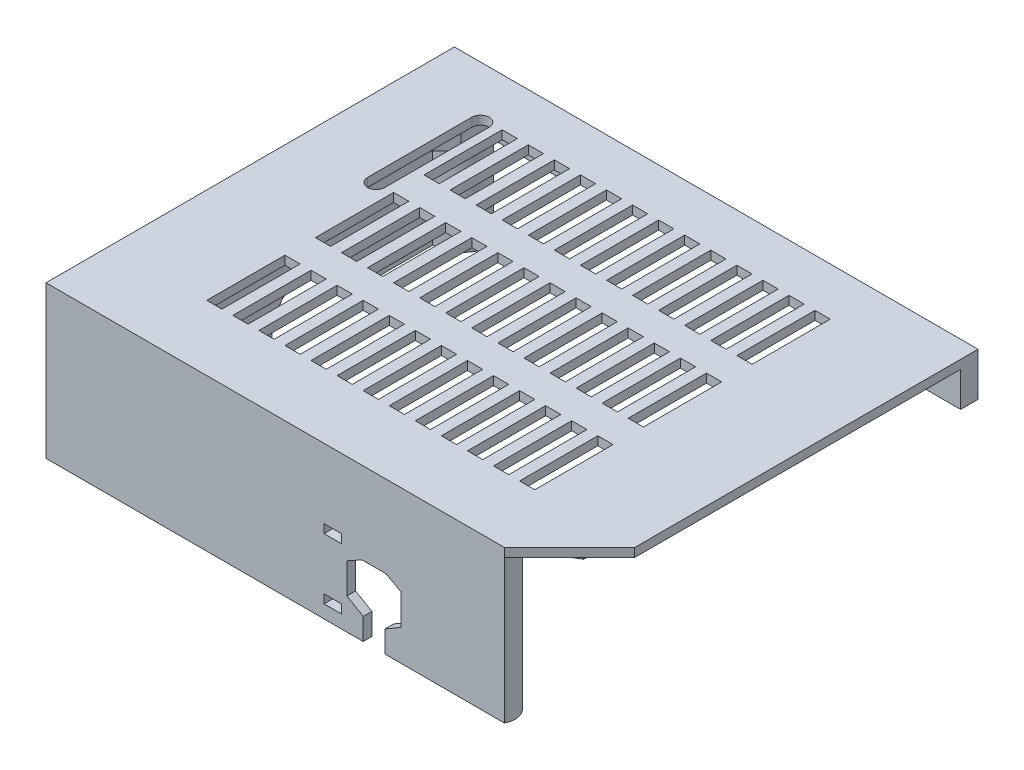
SolidWorks part; units mm, degrees
material "ABS"
ref_plane "Front" through (0, 0, 0) normal (0, 0, 1) x (1, 0, 0)
ref_plane "Top" through (0, 0, 0) normal (0, 1, 0) x (1, 0, 0)
ref_plane "Right" through (0, 0, 0) normal (1, 0, 0) x (0, 0, -1)
sketch "Esquisse1" plane through (0, 0, 0) normal (0, 0, 1) x (1, 0, 0)
  line L0 (0, 0) -> (105.5, 0)
  line L1 (105.5, 0) -> (105.5, -35)
  line L2 (105.5, -35) -> (78, -35)
  line L3 (78, -35) -> (78, -30)
  line L4 (78, -30) -> (81.75, -27.7955)
  line L5 (81.75, -27.7955) -> (81.75, -20.7955)
  line L6 (81.75, -20.7955) -> (78.25, -18.859)
  line L7 (78.25, -18.859) -> (72.75, -18.859)
  line L8 (72.75, -18.859) -> (69.25, -20.7955)
  line L9 (69.25, -20.7955) -> (69.25, -27.7955)
  line L10 (69.25, -27.7955) -> (73, -30)
  line L11 (73, -30) -> (73, -35)
  line L12 (73, -35) -> (0, -35)
  line L13 (0, -35) -> (0, 0)
  line L15 (64, -16) -> (68, -16)
  line L16 (64, -16) -> (64, -18)
  line L17 (64, -18) -> (68, -18)
  line L18 (68, -16) -> (68, -18)
  line L19 (64, -30) -> (68, -30)
  line L20 (64, -30) -> (64, -32)
  line L21 (64, -32) -> (68, -32)
  line L22 (68, -30) -> (68, -32)
  dimension "D1" = 35
  dimension "D2" = 105.5
  dimension "D3" = 5
  dimension "D4" = 4.35
  dimension "D5" = 7
  dimension "D6" = 4
  dimension "D7" = 27.5
  dimension "D8" = 5
  dimension "D9" = 12.5
  dimension "D10" = 5.5
  dimension "D11" = 12
  dimension "D12" = 2
  dimension "D13" = 4
  dimension "D14" = 37.5
  dimension "D15" = 3
extrude "Boss.-Extru.1" add sketch "Esquisse1" along normal blind 2
sketch "Esquisse3" plane through (0, 0, 0) normal (0, 0, -1) x (-1, 0, 0)
  line L0 (-105.5, 0) -> (0, 0) construction
  line L1 (-2, 0) -> (0, 0)
  line L2 (-2, 0) -> (-2, -35)
  line L3 (-2, -35) -> (0, -35)
  line L4 (0, 0) -> (0, -35)
  line L5 (0, -35) -> (-73, -35) construction
  line L6 (0, 0) -> (0, -35) construction
  dimension "D1" = 35
  dimension "D2" = 2
extrude "Boss.-Extru.2" add sketch "Esquisse3" along normal blind 92
sketch "Esquisse4" plane through (0, 0, 0) normal (0, 0, -1) x (-1, 0, 0)
  line L0 (-2, 0) -> (-2, -35) construction
  line L1 (-120.5, 0) -> (-2, 0)
  line L2 (-120.5, 0) -> (-120.5, -2)
  line L3 (-120.5, -2) -> (-2, -2)
  line L4 (-2, 0) -> (-2, -2)
  line L5 (-105.5, 0) -> (-2, 0) construction
  dimension "D1" = 2
  dimension "D2" = 118.5
extrude "Boss.-Extru.3" add sketch "Esquisse4" along normal blind 92 and the other way blind 2
chamfer "Chanfrein3" distance 15 angle 45 1 edges at (120.5, -1, 2)
sketch "Esquisse5" plane through (0, -2, 0) normal (0, -1, 0) x (1, 0, 0)
  line L0 (18, -80) -> (18, -56) construction
  line L1 (16, -80) -> (16, -56)
  line L2 (20, -80) -> (20, -56)
  line L3 (2, 0) -> (2, -92) construction
  line L4 (2, 0) -> (73, 0) construction
  line L5 (120.5, -92) -> (2, -92) construction
  line L6 (22, -81) -> (25.5, -81)
  line L7 (22, -81) -> (22, -63)
  line L8 (22, -63) -> (25.5, -63)
  line L9 (25.5, -81) -> (25.5, -63)
  line L10 (22, -56) -> (25.5, -56)
  line L11 (22, -56) -> (22, -38)
  line L12 (22, -38) -> (25.5, -38)
  line L13 (25.5, -56) -> (25.5, -38)
  line L14 (22, -31) -> (25.5, -31)
  line L15 (22, -31) -> (22, -13)
  line L16 (22, -13) -> (25.5, -13)
  line L17 (25.5, -31) -> (25.5, -13)
  line L18 (28, -31) -> (28, -13)
  line L19 (28, -31) -> (31.5, -31)
  line L20 (31.5, -31) -> (31.5, -13)
  line L21 (28, -13) -> (31.5, -13)
  line L22 (28, -56) -> (28, -38)
  line L23 (28, -56) -> (31.5, -56)
  line L24 (31.5, -56) -> (31.5, -38)
  line L25 (28, -38) -> (31.5, -38)
  line L26 (28, -81) -> (28, -63)
  line L27 (28, -81) -> (31.5, -81)
  line L28 (31.5, -81) -> (31.5, -63)
  line L29 (28, -63) -> (31.5, -63)
  line L30 (34, -31) -> (34, -13)
  line L31 (34, -31) -> (37.5, -31)
  line L32 (37.5, -31) -> (37.5, -13)
  line L33 (34, -13) -> (37.5, -13)
  line L34 (34, -56) -> (34, -38)
  line L35 (34, -56) -> (37.5, -56)
  line L36 (37.5, -56) -> (37.5, -38)
  line L37 (34, -38) -> (37.5, -38)
  line L38 (34, -81) -> (34, -63)
  line L39 (34, -81) -> (37.5, -81)
  line L40 (37.5, -81) -> (37.5, -63)
  line L41 (34, -63) -> (37.5, -63)
  line L42 (40, -31) -> (40, -13)
  line L43 (40, -31) -> (43.5, -31)
  line L44 (43.5, -31) -> (43.5, -13)
  line L45 (40, -13) -> (43.5, -13)
  line L46 (40, -56) -> (40, -38)
  line L47 (40, -56) -> (43.5, -56)
  line L48 (43.5, -56) -> (43.5, -38)
  line L49 (40, -38) -> (43.5, -38)
  line L50 (40, -81) -> (40, -63)
  line L51 (40, -81) -> (43.5, -81)
  line L52 (43.5, -81) -> (43.5, -63)
  line L53 (40, -63) -> (43.5, -63)
  line L54 (46, -31) -> (46, -13)
  line L55 (46, -31) -> (49.5, -31)
  line L56 (49.5, -31) -> (49.5, -13)
  line L57 (46, -13) -> (49.5, -13)
  line L58 (46, -56) -> (46, -38)
  line L59 (46, -56) -> (49.5, -56)
  line L60 (49.5, -56) -> (49.5, -38)
  line L61 (46, -38) -> (49.5, -38)
  line L62 (46, -81) -> (46, -63)
  line L63 (46, -81) -> (49.5, -81)
  line L64 (49.5, -81) -> (49.5, -63)
  line L65 (46, -63) -> (49.5, -63)
  line L66 (52, -31) -> (52, -13)
  line L67 (52, -31) -> (55.5, -31)
  line L68 (55.5, -31) -> (55.5, -13)
  line L69 (52, -13) -> (55.5, -13)
  line L70 (52, -56) -> (52, -38)
  line L71 (52, -56) -> (55.5, -56)
  line L72 (55.5, -56) -> (55.5, -38)
  line L73 (52, -38) -> (55.5, -38)
  line L74 (52, -81) -> (52, -63)
  line L75 (52, -81) -> (55.5, -81)
  line L76 (55.5, -81) -> (55.5, -63)
  line L77 (52, -63) -> (55.5, -63)
  line L78 (58, -31) -> (58, -13)
  line L79 (58, -31) -> (61.5, -31)
  line L80 (61.5, -31) -> (61.5, -13)
  line L81 (58, -13) -> (61.5, -13)
  line L82 (58, -56) -> (58, -38)
  line L83 (58, -56) -> (61.5, -56)
  line L84 (61.5, -56) -> (61.5, -38)
  line L85 (58, -38) -> (61.5, -38)
  line L86 (58, -81) -> (58, -63)
  line L87 (58, -81) -> (61.5, -81)
  line L88 (61.5, -81) -> (61.5, -63)
  line L89 (58, -63) -> (61.5, -63)
  line L90 (64, -31) -> (64, -13)
  line L91 (64, -31) -> (67.5, -31)
  line L92 (67.5, -31) -> (67.5, -13)
  line L93 (64, -13) -> (67.5, -13)
  line L94 (64, -56) -> (64, -38)
  line L95 (64, -56) -> (67.5, -56)
  line L96 (67.5, -56) -> (67.5, -38)
  line L97 (64, -38) -> (67.5, -38)
  line L98 (64, -81) -> (64, -63)
  line L99 (64, -81) -> (67.5, -81)
  line L100 (67.5, -81) -> (67.5, -63)
  line L101 (64, -63) -> (67.5, -63)
  line L102 (70, -31) -> (70, -13)
  line L103 (70, -31) -> (73.5, -31)
  line L104 (73.5, -31) -> (73.5, -13)
  line L105 (70, -13) -> (73.5, -13)
  line L106 (70, -56) -> (70, -38)
  line L107 (70, -56) -> (73.5, -56)
  line L108 (73.5, -56) -> (73.5, -38)
  line L109 (70, -38) -> (73.5, -38)
  line L110 (70, -81) -> (70, -63)
  line L111 (70, -81) -> (73.5, -81)
  line L112 (73.5, -81) -> (73.5, -63)
  line L113 (70, -63) -> (73.5, -63)
  line L114 (76, -31) -> (76, -13)
  line L115 (76, -31) -> (79.5, -31)
  line L116 (79.5, -31) -> (79.5, -13)
  line L117 (76, -13) -> (79.5, -13)
  line L118 (76, -56) -> (76, -38)
  line L119 (76, -56) -> (79.5, -56)
  line L120 (79.5, -56) -> (79.5, -38)
  line L121 (76, -38) -> (79.5, -38)
  line L122 (76, -81) -> (76, -63)
  line L123 (76, -81) -> (79.5, -81)
  line L124 (79.5, -81) -> (79.5, -63)
  line L125 (76, -63) -> (79.5, -63)
  line L126 (82, -31) -> (82, -13)
  line L127 (82, -31) -> (85.5, -31)
  line L128 (85.5, -31) -> (85.5, -13)
  line L129 (82, -13) -> (85.5, -13)
  line L130 (82, -56) -> (82, -38)
  line L131 (82, -56) -> (85.5, -56)
  line L132 (85.5, -56) -> (85.5, -38)
  line L133 (82, -38) -> (85.5, -38)
  line L134 (82, -81) -> (82, -63)
  line L135 (82, -81) -> (85.5, -81)
  line L136 (85.5, -81) -> (85.5, -63)
  line L137 (82, -63) -> (85.5, -63)
  line L138 (88, -31) -> (88, -13)
  line L139 (88, -31) -> (91.5, -31)
  line L140 (91.5, -31) -> (91.5, -13)
  line L141 (88, -13) -> (91.5, -13)
  line L142 (88, -56) -> (88, -38)
  line L143 (88, -56) -> (91.5, -56)
  line L144 (91.5, -56) -> (91.5, -38)
  line L145 (88, -38) -> (91.5, -38)
  line L146 (88, -81) -> (88, -63)
  line L147 (88, -81) -> (91.5, -81)
  line L148 (91.5, -81) -> (91.5, -63)
  line L149 (88, -63) -> (91.5, -63)
  line L150 (94, -31) -> (94, -13)
  line L151 (94, -31) -> (97.5, -31)
  line L152 (97.5, -31) -> (97.5, -13)
  line L153 (94, -13) -> (97.5, -13)
  line L154 (94, -56) -> (94, -38)
  line L155 (94, -56) -> (97.5, -56)
  line L156 (97.5, -56) -> (97.5, -38)
  line L157 (94, -38) -> (97.5, -38)
  line L158 (94, -81) -> (94, -63)
  line L159 (94, -81) -> (97.5, -81)
  line L160 (97.5, -81) -> (97.5, -63)
  line L161 (94, -63) -> (97.5, -63)
  arc A0 (16, -80) -> (20, -80) centre (18, -80) ccw
  arc A1 (20, -56) -> (16, -56) centre (18, -56) ccw
  point P2 (18, -68)
  dimension "D1" = 14
  dimension "D2" = 24
  dimension "D3" = 4
  dimension "D4" = 56
  dimension "D5" = 11
  dimension "D6" = 18
  dimension "D7" = 3.5
  dimension "D8" = 7
  dimension "D9" = 7
  dimension "D10" = 2
  dimension "D11" = 13
extrude "Enlèv. mat.-Extru.1" cut sketch "Esquisse5" against normal blind 92
sketch "Esquisse6" plane through (0, -2, 0) normal (0, -1, 0) x (1, 0, 0)
  line L0 (13.5, 0) -> (13.5, -12)
  line L1 (105.5, 0) -> (2, 0) construction
  line L2 (13.5, -12) -> (5.5, -20)
  line L3 (5.5, -20) -> (2, -20)
  line L4 (2, 0) -> (2, -92) construction
  line L5 (13.5, -92) -> (13.5, -80)
  line L6 (120.5, -92) -> (2, -92) construction
  line L7 (13.5, -80) -> (5.5, -72)
  line L8 (5.5, -72) -> (2, -72)
  line L9 (104.2369, -82) -> (99.4737, -79.25)
  line L10 (99.4737, -79.25) -> (99.4737, -73.75)
  line L11 (99.4737, -73.75) -> (104.2369, -71)
  line L12 (104.2369, -71) -> (109, -73.75)
  line L13 (109, -73.75) -> (109, -79.25)
  line L14 (109, -79.25) -> (104.2369, -82)
  line L15 (104.2369, -21) -> (99.4737, -18.25)
  line L16 (99.4737, -18.25) -> (99.4737, -12.75)
  line L17 (99.4737, -12.75) -> (104.2369, -10)
  line L18 (104.2369, -10) -> (109, -12.75)
  line L19 (109, -12.75) -> (109, -18.25)
  line L20 (109, -18.25) -> (104.2369, -21)
  line L21 (78, 2) -> (105.5, 2) construction
  line L22 (120.5, -13) -> (120.5, -92) construction
  line L23 (2, -20) -> (2, 0)
  line L24 (2, 0) -> (13.5, 0)
  line L25 (2, -72) -> (2, -92)
  line L26 (2, -92) -> (13.5, -92)
  dimension "D1" = 20
  dimension "D2" = 20
  dimension "D3" = 11.5
  dimension "D4" = 135
  dimension "D5" = 3.5
  dimension "D6" = 135
  dimension "D7" = 3.5
  dimension "D8" = 5.5
  dimension "D9" = 5.5
  dimension "D10" = 50
  dimension "D11" = 12
  dimension "D12" = 11.5
  dimension "D13" = 11
  dimension "D14" = 120
  dimension "D15" = 120
  dimension "D16" = 120
  dimension "D17" = 120
extrude "Boss.-Extru.4" add sketch "Esquisse6" along normal blind 6
sketch "Esquisse7" plane through (0, -8, 0) normal (0, -1, 0) x (-1, 0, 0)
  line L0 (-109, 15.5) -> (-99.4737, 15.5) construction
  line L1 (-109, 18.25) -> (-109, 12.75) construction
  line L2 (-99.4737, 12.75) -> (-99.4737, 18.25) construction
  line L3 (-109, 76.5) -> (-99.4737, 76.5) construction
  line L4 (-109, 79.25) -> (-109, 73.75) construction
  line L5 (-99.4737, 73.75) -> (-99.4737, 79.25) construction
  line L6 (-104.2369, 10) -> (-104.2369, 21) construction
  line L7 (-104.2369, 21) -> (-104.2369, 82) construction
  circle A0 centre (-104.2369, 15.5) radius 2.5
  circle A1 centre (-104.2369, 76.5) radius 2.5
  circle A2 centre (-5.4987, 76.5) radius 2.5
  circle A3 centre (-5.4987, 15.5) radius 2.5
  dimension "D1" = 5
extrude "Enlèv. mat.-Extru.2" cut sketch "Esquisse7" against normal blind 4
sketch "Esquisse8" plane through (0, -2, 0) normal (0, -1, 0) x (1, 0, 0)
  line L0 (2, -92) -> (2, 0) construction
  line L1 (13.5, 0) -> (2, 0) construction
  line L2 (2, -92) -> (13.5, -92) construction
  line L3 (56, 0) -> (56, -3.5)
  line L4 (105.5, 0) -> (13.5, 0) construction
  line L5 (56, -3.5) -> (58.8028, -6.3028)
  line L6 (58.8028, -6.3028) -> (62.6972, -6.3028)
  line L7 (62.6972, -6.3028) -> (65.5, -3.5)
  line L8 (65.5, -3.5) -> (65.5, 0)
  line L9 (65.5, 0) -> (56, 0)
  line L10 (2, 0) -> (9, 0)
  line L11 (2, -7) -> (2, 0)
  line L12 (2, -85) -> (2, -92)
  line L13 (2, -92) -> (9, -92)
  line L14 (120.5, -92) -> (13.5, -92) construction
  line L15 (65.5, 0) -> (71, 0)
  line L16 (65.5, 0) -> (65.5, -1.5)
  line L17 (65.5, -1.5) -> (71, -1.5)
  line L18 (71, 0) -> (71, -1.5)
  line L19 (7.7446, -88) -> (31.7446, -88)
  line L22 (31.7446, -88) -> (31.7446, -92)
  line L23 (120.5, -13) -> (120.5, -92) construction
  line L25 (31.7446, -88) -> (31.7446, -92)
  line L27 (96.5, -88) -> (96.5, -92)
  line L32 (96.5, -92) -> (120.5, -92)
  line L34 (96.5, -88) -> (120.5, -88)
  line L35 (120.5, -92) -> (120.5, -88)
  line L36 (96.5, -88) -> (96.5, -92)
  line L37 (31.7446, -92) -> (9, -92)
  line L38 (0, 2) -> (0, -92) construction
  line L39 (105.5, 2) -> (98.5359, 2)
  line L41 (31.7446, -89) -> (96.5, -89)
  line L42 (31.7446, -89) -> (31.7446, -92)
  line L43 (31.7446, -92) -> (96.5, -92)
  line L44 (96.5, -89) -> (96.5, -92)
  arc A0 (2, -7) -> (9, 0) centre (2, 0) ccw
  arc A1 (2, -85) -> (9, -92) centre (2, -92) cw
  circle A2 centre (102, 0) radius 4
  dimension "D9" = 102
  dimension "D10" = 8
  dimension "D1" = 9.5
  dimension "D2" = 3.5
  dimension "D3" = 54
  dimension "D4" = 6.3028
  dimension "D5" = 5.5
  dimension "D6" = 1.5
  dimension "D7" = 7
  dimension "D8" = 7
  dimension "D11" = 4
  dimension "D12" = 22.7446
  dimension "D13" = 24
  dimension "D14" = 3
extrude "Boss.-Extru.5" add sketch "Esquisse8" along normal up to surface (33 mm away) contours L39 A2 | L8 L9 L3 L5 L6 L7 | A1 L12 L13 | L10 A0 L11 region at (60.75, -2, -2.8166) region at (4.9709, -2, -89.0291) region at (102, -2, -0.6853) up to face at (25, -35, -30)
extrude "Boss.-Extru.9" add sketch "Esquisse8<5>" along normal blind 3 contours L25 L43 L36 L41 | L15 L18 L17 L16 region at (64.1223, -2, -90.5)
sketch "Esquisse8<5>" plane through (0, -2, 0) normal (0, -1, 0) x (1, 0, 0) same geometry as "Esquisse8"
extrude "Boss.-Extru.12" add sketch "Esquisse8<6>" along normal blind 8 contours L19 A1 L37 L25 L22 | L32 L35 L34 L27 L36 region at (20.1682, -2, -89.9823) region at (108.5, -2, -90)
sketch "Esquisse8<6>" plane through (0, -2, 0) normal (0, -1, 0) x (1, 0, 0) same geometry as "Esquisse8"
sketch "Esquisse9" plane through (0, -35, 0) normal (0, -1, 0) x (1, 0, 0)
  line L0 (0, 2) -> (73, 2) construction
  line L1 (0, 2) -> (0, -92) construction
  line L2 (9, -92) -> (0, -92) construction
  line L4 (56, -3.5) -> (56, 0) construction
  circle A0 centre (3.5, -1.5) radius 2
  circle A1 centre (60.75, -1.5) radius 2
  circle A2 centre (3.5, -88.5) radius 2
  dimension "D1" = 4
  dimension "D2" = 3.5
  dimension "D3" = 3.5
  dimension "D4" = 3.5
  dimension "D5" = 4.75
extrude "Enlèv. mat.-Extru.3" cut sketch "Esquisse9" against normal blind 5
sketch "Esquisse10" plane through (0, 0, -92) normal (0, 0, -1) x (-1, 0, 0)
  line L0 (0, 0) -> (-120.5, 0) construction
  line L1 (0, -35) -> (0, 0) construction
  circle A0 centre (-108, -5) radius 2.5
  circle A1 centre (-18, -5) radius 2.5
  dimension "D1" = 5
  dimension "D2" = 18
  dimension "D3" = 90
  dimension "D4" = 5
extrude "Enlèv. mat.-Extru.4" cut sketch "Esquisse10" against normal blind 5
sketch "Esquisse11" plane through (0, 0, 0) normal (-1, 0, 0) x (0, 0, 1)
  line L0 (2, -35) -> (-92, -35) construction
  line L1 (-43, -10) -> (-28, -10)
  line L2 (-43, -10) -> (-43, -20)
  line L3 (-43, -20) -> (-28, -20)
  line L4 (-28, -10) -> (-28, -20)
  line L5 (-73, -35) -> (-68, -35)
  line L6 (-48, -35) -> (-43, -35)
  line L7 (2, 0) -> (2, -35) construction
  line L8 (2, 0) -> (-92, 0) construction
  arc A0 (-68, -35) -> (-48, -35) centre (-58, -35) cw
  arc A1 (-43, -35) -> (-73, -35) centre (-58, -35) ccw
  line M9 (-92, -35) -> (2, -35)
  dimension "D1" = 10
  dimension "D2" = 15
  dimension "D3" = 60
  dimension "D4" = 30
  dimension "D5" = 10
  dimension "D6" = 15
  dimension "D7" = 10
extrude "Boss.-Extru.13" add sketch "Esquisse11" along normal blind 10 draft 15 contours L6 A1 L5 A0
extrude "Enlèv. mat.-Extru.7" cut sketch "Esquisse11<4>" against normal blind 2 contours A0 M9 | L4 L1 L2 L3 region at (0, -15, -35.5) region at (0, -30.7559, -58)
sketch "Esquisse11<4>" plane through (0, 0, 0) normal (-1, 0, 0) x (0, 0, 1) same geometry as "Esquisse11"
